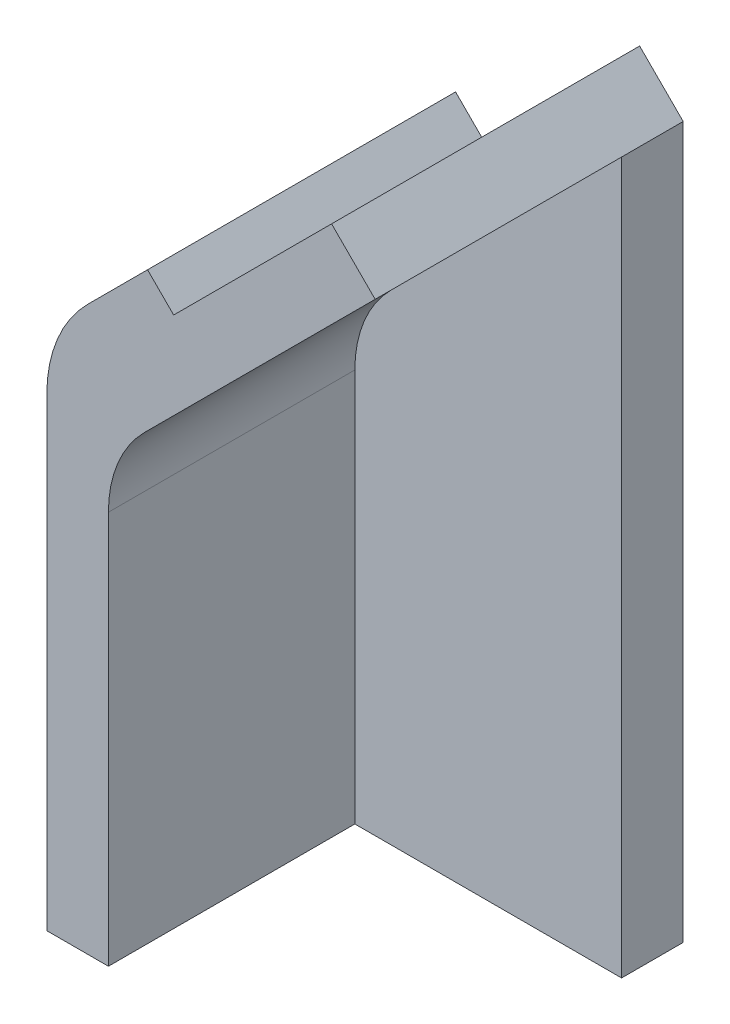
SolidWorks part; units mm, degrees
ref_plane "Front Plane" through (0, 0, 0) normal (0, 0, 1) x (1, 0, 0)
ref_plane "Top Plane" through (0, 0, 0) normal (0, 1, 0) x (1, 0, 0)
ref_plane "Right Plane" through (0, 0, 0) normal (1, 0, 0) x (0, 0, -1)
sketch "Sketch1" plane through (-44.3957, 24.7263, -28.895) normal (0, 0, 1) x (0.7071, -0.7071, 0)
  line L0 (4.8, 0) -> (3.5964, 0) construction
  line L1 (4.8, 7) -> (4.8, 0) construction
  line L2 (4.8, 0) -> (3.6, 0)
  line L3 (4.8, 7) -> (4.8, 0)
  line L4 (15.6568, -17.0347) -> (4.9986, -6.3764) construction
  line L5 (3.6, -3) -> (3.6, 0) construction
  line L6 (15.6568, -17.0347) -> (4.9986, -6.3764)
  line L7 (3.6, -3) -> (3.6, 0)
  arc A0 (3.6, -3) -> (4.9986, -6.3764) centre (8.375, -3) ccw construction
  arc A1 (3.6, -3) -> (4.9986, -6.3764) centre (8.375, -3) ccw
sketch "Sketch2" plane through (-44.3957, 24.7263, -28.895) normal (0, 0, 1) x (0.7071, -0.7071, 0)
  line L8 (5.05, 7) -> (7.05, 7)
  line L9 (7.05, 7) -> (7.05, -3.589)
  line L10 (8.2216, -6.4175) -> (17.2478, -15.4437)
  line L11 (17.2478, -15.4437) -> (15.8336, -16.8579)
  line L38 (5.05, -0.25) -> (5.05, 7)
  line L39 (3.85, -0.25) -> (5.05, -0.25)
  line L40 (3.85, -3) -> (3.85, -0.25)
  line L41 (15.8336, -16.8579) -> (5.1753, -6.1997)
  line L42 (5.05, -0.25) -> (5.05, 7)
  line L43 (3.85, -0.25) -> (5.05, -0.25)
  line L44 (3.85, -3) -> (3.85, -0.25)
  line L45 (15.8336, -16.8579) -> (5.1753, -6.1997)
  arc A2 (7.05, -3.589) -> (8.2216, -6.4175) centre (11.05, -3.589) ccw
  arc A12 (3.85, -3) -> (5.1753, -6.1997) centre (8.375, -3) ccw
  arc A13 (3.85, -3) -> (5.1753, -6.1997) centre (8.375, -3) ccw
  dimension "D1" = 2
  dimension "D3" = 4
  dimension "D2" = 0.25
extrude "Boss-Extrude1" add sketch "Sketch2" along normal mid plane 10
sketch "Sketch3" plane through (0, 0, -33.895) normal (0, 0, -1) x (-1, 0, 0)
  line L0 (34.4608, 24.691) -> (34.4608, 1.61)
  line L1 (34.4608, 1.61) -> (43.12, 1.61)
  line L2 (41.9484, 17.2034) -> (34.4608, 24.691) construction
  line L3 (43.12, 1.61) -> (43.12, 14.375) construction
  line L4 (41.9484, 17.2034) -> (34.4608, 24.691)
  line L5 (43.12, 1.61) -> (43.12, 14.375)
  arc A0 (43.12, 14.375) -> (41.9484, 17.2034) centre (39.12, 14.375) ccw construction
  arc A1 (43.12, 14.375) -> (41.9484, 17.2034) centre (39.12, 14.375) ccw
extrude "Boss-Extrude2" add sketch "Sketch3" against normal blind 2
